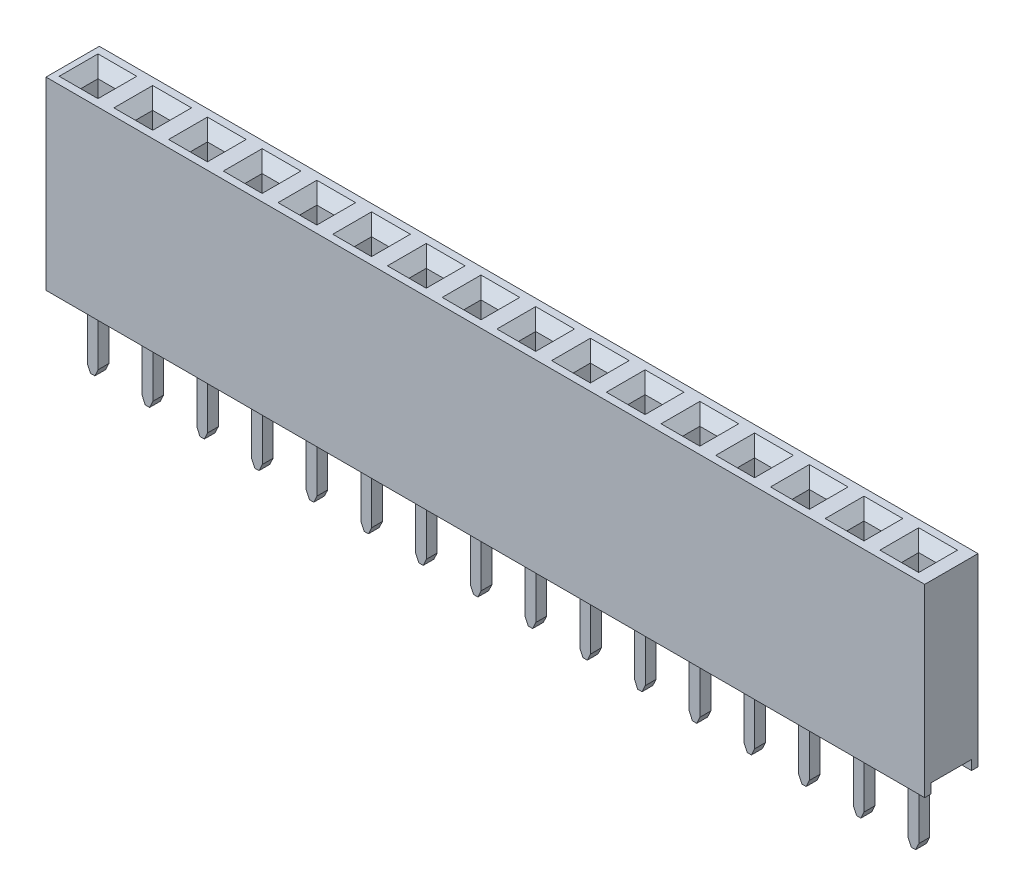
SolidWorks part; units mm, degrees
note: The reader was unsure of these and kept them because the rebuilt part matched: shared geometry of "Sketch9<3>".
ref_plane "Front" through (0, 0, 0) normal (0, 0, 1) x (1, 0, 0)
ref_plane "Top" through (0, 0, 0) normal (0, 1, 0) x (1, 0, 0)
ref_plane "Right" through (0, 0, 0) normal (1, 0, 0) x (0, 0, -1)
sketch "Sketch1" plane through (0, 0, 0) normal (0, 0, 1) x (1, 0, 0)
  line L1 (20.395, -4.2875) -> (-20.395, -4.2875)
  line L2 (20.395, -4.2875) -> (20.395, 4.2875)
  line L3 (20.395, 4.2875) -> (-20.395, 4.2875)
  line L4 (-20.395, -4.2875) -> (-20.395, 4.2875)
  line L5 (20.395, -4.2875) -> (-20.395, 4.2875) construction
  line L6 (20.395, 4.2875) -> (-20.395, -4.2875) construction
  point P0 (0, 0)
  dimension "D1" = 40.79
  dimension "D2" = 8.575
extrude "Boss-Extrude1" add sketch "Sketch1" along normal mid plane 2.475
sketch "Sketch2" plane through (0, 0, 0) normal (1, 0, 0) x (0, 0, -1)
  line L0 (-0.9375, -4.2875) -> (0.9375, -4.2875)
  line L1 (-1.2375, -4.2875) -> (1.2375, -4.2875) construction
  line L2 (0.9375, -4.2875) -> (0.9375, -3.8396)
  line L3 (0.9375, -3.8396) -> (-0.9375, -3.8396)
  line L4 (-0.9375, -3.8396) -> (-0.9375, -4.2875)
  line L5 (1.2375, -4.2875) -> (1.2375, 4.2875) construction
  line L6 (-1.2375, -4.2875) -> (-1.2375, 4.2875) construction
  dimension "D1" = 0.3
  dimension "D2" = 0.3
extrude "Cut-Extrude1" cut sketch "Sketch2" against normal mid plane 100
sketch "Sketch4" plane through (0, 4.2875, 0) normal (0, 1, 0) x (1, 0, 0)
  line L0 (-20.395, 0) -> (20.395, 0) construction
  line L1 (-20.395, -1.2375) -> (-20.395, 1.2375) construction
  line L2 (20.395, -1.2375) -> (20.395, 1.2375) construction
  line L4 (-20.095, 0.875) -> (-18.345, 0.875)
  line L5 (-20.095, 0.875) -> (-20.095, -0.875)
  line L6 (-20.095, -0.875) -> (-18.345, -0.875)
  line L7 (-18.345, 0.875) -> (-18.345, -0.875)
  line L8 (-20.095, 0.875) -> (-18.345, -0.875) construction
  line L9 (-20.095, -0.875) -> (-18.345, 0.875) construction
  line L10 (-19.62, 0.4) -> (-18.82, 0.4)
  line L11 (-19.62, 0.4) -> (-19.62, -0.4)
  line L12 (-19.62, -0.4) -> (-18.82, -0.4)
  line L13 (-18.82, 0.4) -> (-18.82, -0.4)
  line L14 (-19.62, 0.4) -> (-18.82, -0.4) construction
  line L15 (-19.62, -0.4) -> (-18.82, 0.4) construction
  point P6 (-19.22, 0)
  point P11 (-19.22, 0)
  dimension "D1" = 1.75
  dimension "D2" = 0.8
  dimension "D3" = 0.3
extrude "Cut-Extrude2" cut sketch "Sketch4" against normal blind 1.5 contours L13 L10 L11 L12
chamfer "Chamfer1" distance 0.5 angle 45 4 edges at (-19.22, 4.2875, -0.4) (-19.62, 4.2875, 0) (-19.22, 4.2875, 0.4) (-18.82, 4.2875, 0)
sketch "Sketch5" plane through (0, 0, 0) normal (0, 1, 0) x (1, 0, 0)
  line L1 (-20.12, 0.9) -> (-18.32, 0.9)
  line L2 (-20.12, 0.9) -> (-20.12, -0.9)
  line L3 (-20.12, -0.9) -> (-18.32, -0.9)
  line L4 (-18.32, 0.9) -> (-18.32, -0.9)
extrude "Cut-Extrude3" cut sketch "Sketch5" against normal blind 3 and the other way blind 3
sketch "Sketch9" plane through (0, 0, 0) normal (0, 0, 1) x (1, 0, 0)
  line L0 (-19.2134, 1.6839) -> (-19.2134, -6.1854) construction
  line L1 (-18.32, -1.2586) -> (-18.348, -1.1406)
  line L2 (-18.348, -1.1406) -> (-18.798, 1.5706)
  line L3 (-18.9294, 1.4044) -> (-18.7022, -1.9066)
  line L4 (-18.32, -1.2586) -> (-18.32, -2.6102)
  line L5 (-18.32, -2.6102) -> (-18.592, -2.9702)
  line L6 (-18.592, -2.9702) -> (-19.848, -2.9702)
  line L7 (-20.12, -2.6102) -> (-19.848, -2.9702)
  line L8 (-20.12, -1.2586) -> (-20.12, -2.6102)
  line L9 (-20.12, -1.2586) -> (-20.092, -1.1406)
  line L10 (-20.092, -1.1406) -> (-19.642, 1.5706)
  line L11 (-19.5106, 1.4044) -> (-19.7378, -1.9066)
  line L12 (-19.3134, -7.5787) -> (-19.1134, -7.5787)
  line L13 (-19.1134, -7.5787) -> (-18.9634, -7.257)
  line L14 (-18.9634, -7.257) -> (-18.9634, -2.9702)
  line L15 (-19.3134, -7.5787) -> (-19.4634, -7.257)
  line L16 (-19.4634, -7.257) -> (-19.4634, -2.9702)
  line L19 (-20.12, 3) -> (-20.12, -3) construction
  line L20 (-18.32, 3) -> (-18.32, -3) construction
  arc A0 (-18.798, 1.5706) -> (-18.9294, 1.4044) centre (-18.9392, 1.5472) ccw
  arc A1 (-18.7022, -1.9066) -> (-19.22, -2.3264) centre (-19.1087, -1.9345) cw
  arc A2 (-19.7378, -1.9066) -> (-19.22, -2.3264) centre (-19.3313, -1.9345) ccw
  arc A3 (-19.642, 1.5706) -> (-19.5106, 1.4044) centre (-19.5008, 1.5472) cw
  point P16 (-19.2134, -2.9702)
  point P24 (-19.4634, -4.2787)
extrude "Boss-Extrude4" add sketch "Sketch9" along normal mid plane 1.7 contours A1 L0 L6 L5 L4 L1 L2 A0 L3 | L0 A2 L11 A3 L10 L9 L8 L7 L6 | L14 L13 L12 L15 L16
extrude "Boss-Extrude5" add sketch "Sketch9<3>" along normal mid plane 0.5
sketch "Sketch9<3>" plane through (0, 0, 0) normal (0, 0, 1) x (1, 0, 0) same geometry as "Sketch9"
pattern_linear "LPattern1" count 16 spacing 2.54 along (1, 0, 0) of "Cut-Extrude2", "Chamfer1", "Cut-Extrude3", "Boss-Extrude4", "Boss-Extrude5"
